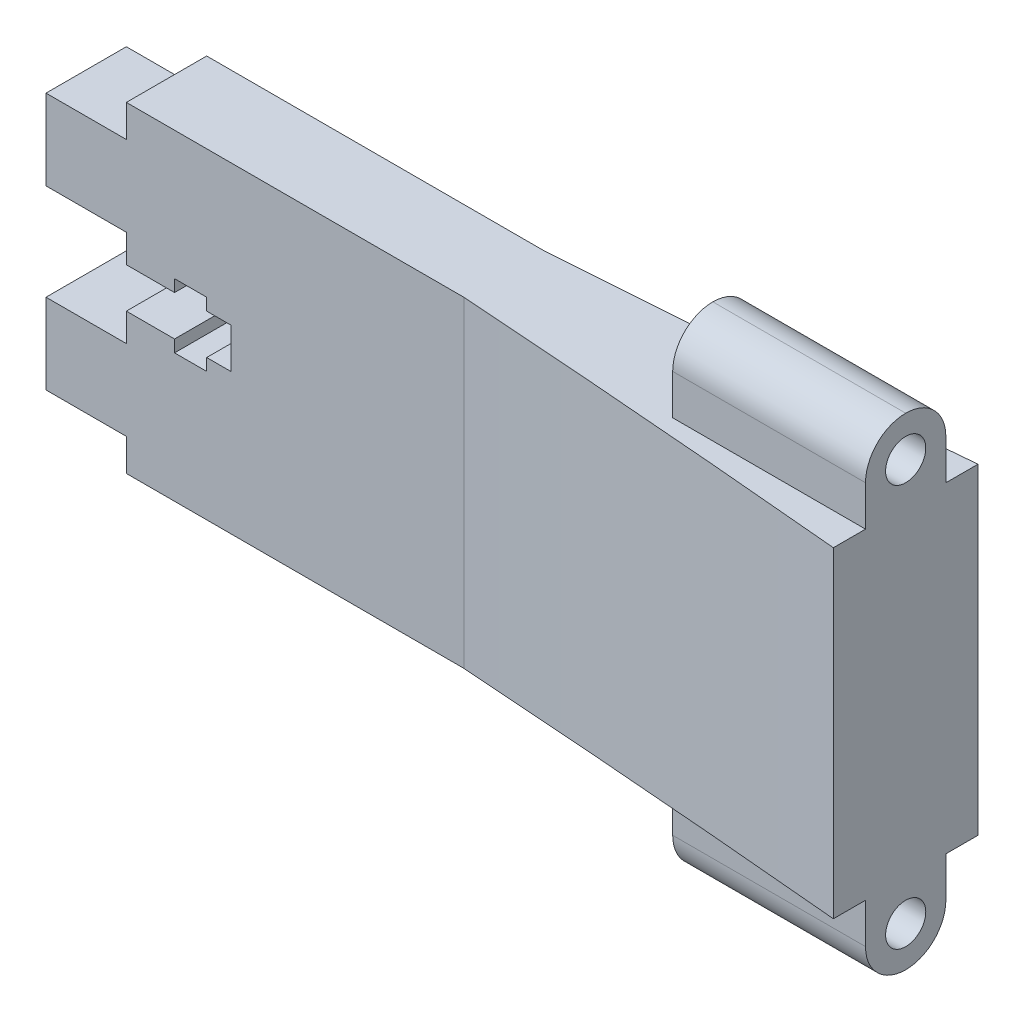
SolidWorks part; units mm, degrees
ref_plane "Front Plane" through (0, 0, 0) normal (0, 0, 1) x (1, 0, 0)
ref_plane "Top Plane" through (0, 0, 0) normal (0, 1, 0) x (1, 0, 0)
ref_plane "Right Plane" through (0, 0, 0) normal (1, 0, 0) x (0, 0, -1)
sketch "Sketch1" plane through (0, 0, 0) normal (0, 0, 1) x (1, 0, 0)
  line L5 (-36, 4) -> (-36, 2.5)
  line L6 (22, -20) -> (-46, -20)
  line L18 (0, 0) -> (0, -12.9172) construction
  line L42 (22, 20) -> (-46, 20)
  line L43 (-46, -20) -> (-46, -16)
  line L44 (46, -20) -> (-46, 20) construction
  line L45 (46, 20) -> (-46, -20) construction
  line L46 (-33, -2.5) -> (-36, -2.5)
  line L47 (-33, -2.5) -> (-33, 2.5)
  line L48 (-33, 2.5) -> (-36, 2.5)
  line L49 (-40, 4) -> (-40, 2.5)
  line L50 (-40, -4) -> (-36, -4)
  line L51 (-40, 4) -> (-36, 4)
  line L52 (-40, -2.5) -> (-46, -2.5)
  line L53 (-40, 2.5) -> (-46, 2.5)
  line L54 (-40, -2.5) -> (-40, -4)
  line L55 (-36, -2.5) -> (-36, -4)
  line L56 (0, 0) -> (-13.3376, 0) construction
  line L57 (-46, 2.5) -> (-46, 6)
  line L58 (-46, -16) -> (-56, -16)
  line L59 (-46, -6) -> (-56, -6)
  line L60 (-56, -16) -> (-56, -6)
  line L61 (-46, -6) -> (-46, -2.5)
  line L62 (-46, 16) -> (-56, 16)
  line L63 (-56, 16) -> (-56, 6)
  line L66 (-46, 6) -> (-56, 6)
  line L67 (-46, 16) -> (-46, 20)
  line L68 (46, -20) -> (46, -16)
  line L72 (46, -6) -> (46, -2.5)
  line L73 (46, -20) -> (46, -30)
  line L74 (46, -30) -> (22, -30)
  line L75 (22, -30) -> (22, -20)
  line L76 (46, 20) -> (46, 30)
  line L77 (46, 30) -> (22, 30)
  line L78 (22, 30) -> (22, 20)
  line L79 (46, 16) -> (46, 6)
  line L80 (46, -6) -> (46, -16)
  line L84 (46, 2.5) -> (46, 6)
  line L88 (46, 16) -> (46, 20)
  line L89 (46, 2.5) -> (46, -2.5)
  point P0 (0, 0)
  dimension "D15" = 24
  dimension "D1" = 40
  dimension "D2" = 92
  dimension "D3" = 17.5
  dimension "D4" = 22.5
  dimension "D5" = 13
  dimension "D6" = 3
  dimension "D7" = 4
  dimension "D8" = 8
  dimension "D9" = 1.5
  dimension "D10" = 4
  dimension "D11" = 10
  dimension "D12" = 10
  dimension "D13" = 24
  dimension "D14" = 10
  dimension "D16" = 10
  dimension "D17" = 0
  dimension "D18" = 0
extrude "Boss-Extrude1" add sketch "Sketch1" along normal mid plane 10 contours L42 L67 L62 L63 L66 L57 L53 L49 L51 L5 L48 L47 L46 L55 L50 L54 L52 L61 L59 L60 L58 L43 L6 region at (2.1348, 0, 0)
sketch "Sketch2" plane through (22, 0, 0) normal (-1, 0, 0) x (0, 0, 1)
  line L0 (5, -30) -> (-5, -30) construction
  line L1 (-5, -30) -> (-5, -20) construction
  circle A0 centre (0, -25) radius 2.5
  dimension "D2" = 5
  dimension "D1" = 5
  dimension "D3" = 5
extrude "Cut-Extrude1" cut sketch "Sketch2" against normal through all
sketch "Sketch3" plane through (22, 0, 0) normal (-1, 0, 0) x (0, 0, 1)
  line L0 (5, 30) -> (5, 20) construction
  line L1 (5, 30) -> (-5, 30) construction
  circle A0 centre (0, 25) radius 2.5
  dimension "D2" = 5
  dimension "D1" = 5
  dimension "D3" = 5
extrude "Cut-Extrude2" cut sketch "Sketch3" against normal through all
fillet "Fillet1" radius 5 4 edges at (34, -30, 5) (34, -30, -5) (34, 30, 5) (34, 30, -5)
sketch "Çizim2" plane through (0, 0, 0) normal (0, 1, 0) x (1, 0, 0)
  line L3 (46, 5) -> (-4, 5)
  line L4 (46, 5) -> (46, 9)
  spline S0 degree 2 poles (-4, 5) (21.0251, 6.6976) (46, 9) knots 0 0 0 1 1 1
  dimension "D1" = 5
  dimension "D2" = 50
  dimension "D3" = 4
  dimension "D4" = 46
  dimension "D5" = 2.86
  dimension "D6" = 12.8
extrude "Yükseklik-Ekstrüzyon1" add sketch "Çizim2" along normal mid plane 40
mirror "Mirror1" about plane through (0, 0, 0) normal (0, 0, 1) of "Yükseklik-Ekstrüzyon1"
